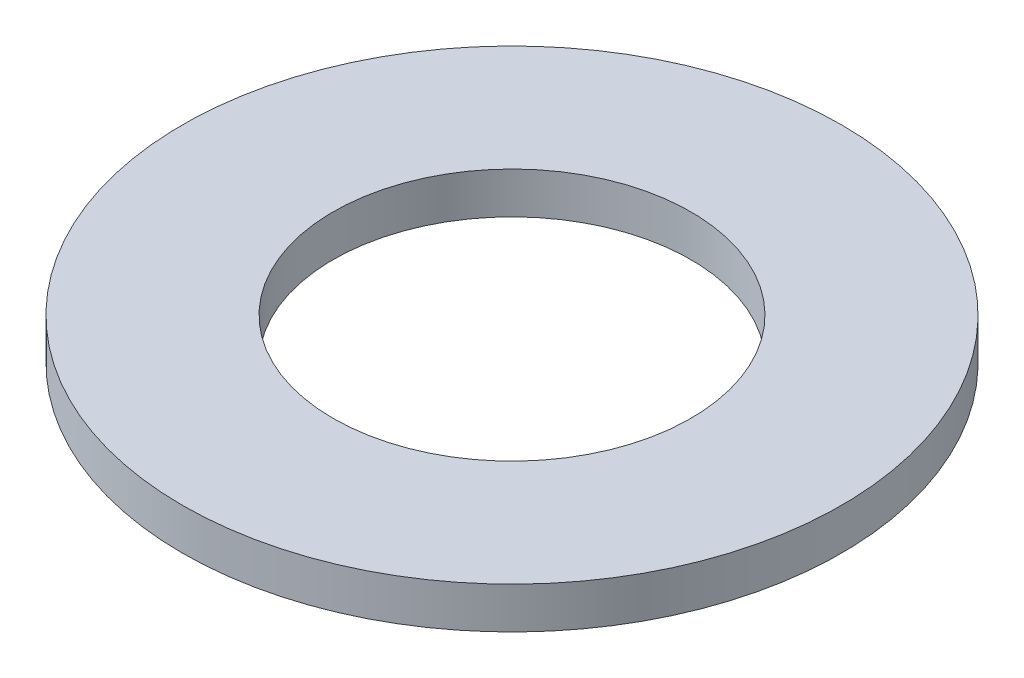
SolidWorks part; units mm, degrees
ref_plane "Front Plane" through (0, 0, 0) normal (0, 0, 1) x (1, 0, 0)
ref_plane "Top Plane" through (0, 0, 0) normal (0, 1, 0) x (1, 0, 0)
ref_plane "Right Plane" through (0, 0, 0) normal (1, 0, 0) x (0, 0, -1)
sketch "Sketch1" plane through (0, 0, 0) normal (0, 1, 0) x (1, 0, 0)
  circle A0 centre (0, 0) radius 87.5
  dimension "FLANGE_OD" = 175
extrude "Boss-Extrude1" add sketch "Sketch1" along normal blind 11
sketch "Sketch2" plane through (0, 0, 0) normal (0, 1, 0) x (1, 0, 0)
  circle A0 centre (0, 0) radius 47.5
  dimension "BORE_D" = 95
extrude "Cut-Extrude1" cut sketch "Sketch2" along normal through all
sketch "Sketch3" plane through (0, 11, 0) normal (0, 1, 0) x (1, 0, 0)
  circle A0 centre (0, 0) radius 31.6336 construction
  circle A1 centre (-31.6336, 0) radius 4.6892
  dimension "BOLT_D" = 9.3785
  dimension "BOLT_PCD" = 63.2673
extrude "Cut-Extrude2" cut sketch "Sketch3" against normal blind 9.3088 rebuild error yes
pattern_circular "CirPattern1" count 4 over 360 rebuild error yes
